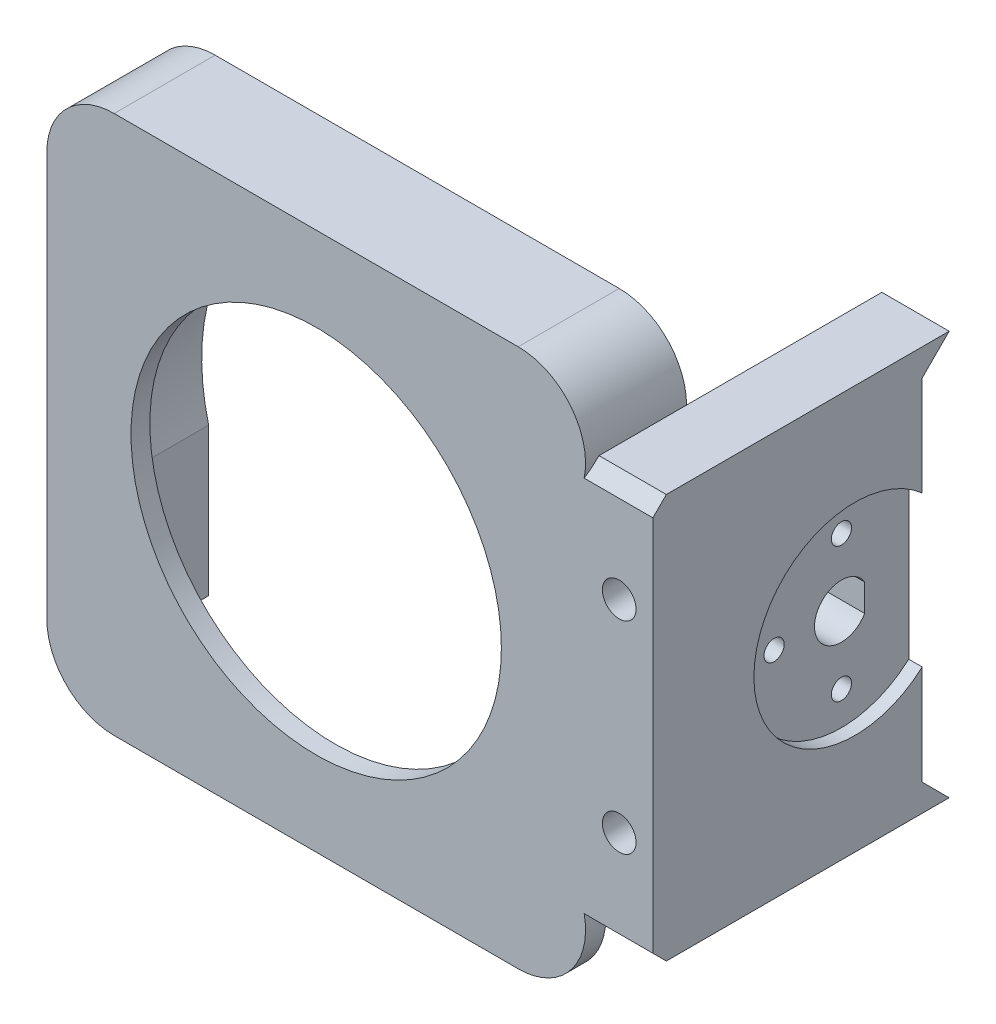
SolidWorks part; units mm, degrees
ref_plane "Front Plane" through (0, 0, 0) normal (0, 0, 1) x (1, 0, 0)
ref_plane "Top Plane" through (0, 0, 0) normal (0, 1, 0) x (1, 0, 0)
ref_plane "Right Plane" through (0, 0, 0) normal (1, 0, 0) x (0, 0, -1)
sketch "Sketch1" plane through (0, 0, 0) normal (0, 0, 1) x (1, 0, 0)
  line L1 (0, 0) -> (80, 0)
  line L2 (0, 0) -> (0, 80)
  line L3 (0, 80) -> (80, 80)
  line L4 (80, 0) -> (80, 80)
  circle A0 centre (40, 40) radius 32
  dimension "D3" = 64
  dimension "D1" = 80
  dimension "D2" = 80
extrude "Boss-Extrude1" add sketch "Sketch1" along normal blind 15
sketch "Sketch2" plane through (0, 0, 15) normal (0, 0, 1) x (1, 0, 0)
  circle A0 centre (40, 40) radius 32
  circle A1 centre (40, 40) radius 27.5
  dimension "D1" = 55
  dimension "D2" = 64
extrude "Boss-Extrude2" add sketch "Sketch2" against normal blind 2.8
fillet "Fillet1" radius 10 4 edges at (80, 0, 7.5) (0, 0, 7.5) (0, 80, 7.5) (80, 80, 7.5)
sketch "Sketch4" plane through (80, 0, 0) normal (1, 0, 0) x (0, 0, -1)
  line L1 (-15, 70) -> (25, 70)
  line L2 (-15, 70) -> (-15, 10)
  line L3 (-15, 10) -> (25, 10)
  line L4 (25, 70) -> (25, 10)
  dimension "D1" = 40
extrude "Boss-Extrude3" add sketch "Sketch4" along normal blind 10
sketch "Sketch10" plane through (0, 0, -25) normal (0, 0, -1) x (-1, 0, 0)
  line L0 (-90, 70) -> (-80, 70) construction
  line L1 (-90, 40) -> (-80, 40) construction
  line L2 (-90, 10) -> (-90, 70) construction
  line L3 (-80, 10) -> (-80, 70) construction
  circle A0 centre (-85, 55) radius 2.5
  circle A1 centre (-85, 25) radius 2.5
  dimension "D1" = 15
  dimension "D2" = 5
extrude "Cut-Extrude2" cut sketch "Sketch10" against normal through all
chamfer "Chamfer1" distance 2 angle 45 2 edges at (85, 10, 15) (85, 70, 15)
sketch "Sketch11" plane through (90, 0, 0) normal (1, 0, 0) x (0, 0, -1)
  line L0 (25, 70) -> (25, 66)
  line L1 (25, 10) -> (25, 70) construction
  line L2 (25, 66) -> (29, 70)
  line L3 (29, 70) -> (25, 70)
  line L4 (25, 40) -> (18.4514, 40) construction
  line L5 (25, 14) -> (29, 10)
  line L6 (25, 10) -> (25, 14)
  line L7 (29, 10) -> (25, 10)
  dimension "D1" = 4
  dimension "D2" = 4
extrude "Boss-Extrude7" add sketch "Sketch11" against normal blind 10
sketch "Sketch12" plane through (90, 0, 0) normal (1, 0, 0) x (0, 0, -1)
  line L0 (-15, 40) -> (15, 40) construction
  line L1 (-15, 68) -> (-15, 12) construction
  line L2 (18.4517, 42.0213) -> (18.4517, 37.9787)
  arc A0 (18.4517, 42.0213) -> (18.4517, 37.9787) centre (15, 40) ccw
  dimension "D2" = 8
  dimension "D1" = 30
extrude "Cut-Extrude3" cut sketch "Sketch12" against normal blind 10
sketch "Sketch13" plane through (90, 0, 0) normal (1, 0, 0) x (0, 0, -1)
  circle A0 centre (15, 40) radius 10
  circle A1 centre (15, 50) radius 1.5
  circle A3 centre (15, 40) radius 10
  circle A4 centre (15, 30) radius 1.5
  circle A5 centre (15, 40) radius 10
  circle A6 centre (5, 40) radius 1.5
  circle A7 centre (15, 40) radius 10
  arc A8 (24.925, 41.4981) -> (24.925, 38.5019) centre (25, 40) ccw [skipped]
  point P17 (15, 40)
  dimension "D1" = 20
  dimension "D2" = 3
  dimension "D3" = 4
extrude "Cut-Extrude5" cut sketch "Sketch13" against normal blind 30 contours A6 | A1 | A4
sketch "Sketch14" plane through (90, 0, 0) normal (1, 0, 0) x (0, 0, -1)
  circle A0 centre (15, 40) radius 15
  dimension "D1" = 30
extrude "Cut-Extrude6" cut sketch "Sketch14" against normal blind 2
sketch "Sketch16" plane through (0, 0, 0) normal (0, 0, -1) x (-1, 0, 0)
  line L1 (-70, 0) -> (-9.0323, 0)
  line L2 (-70, 0) -> (-70, 31.9378)
  line L3 (-70, 31.9378) -> (-9.0323, 31.9378)
  line L4 (-9.0323, 0) -> (-9.0323, 31.9378)
  circle A0 centre (-40, 40) radius 32 construction
extrude "Cut-Extrude10" cut sketch "Sketch16" against normal blind 12
sketch "Sketch17" plane through (0, 0, 0) normal (0, 0, -1) x (-1, 0, 0)
  line L1 (-80, 10) -> (0, 10)
  line L2 (-80, 10) -> (-80, 0)
  line L3 (-80, 0) -> (0, 0)
  line L4 (0, 10) -> (0, 0)
extrude "Cut-Extrude11" cut sketch "Sketch17" against normal blind 12
sketch "Sketch18" plane through (0, 10, 0) normal (0, -1, 0) x (1, 0, 0)
  circle A0 centre (5, 6) radius 2
  circle A1 centre (75, 6) radius 2
  dimension "D1" = 4
  dimension "D2" = 4
extrude "Cut-Extrude12" cut sketch "Sketch18" against normal blind 20
sketch "Sketch19" plane through (0, 30, 0) normal (0, -1, 0) x (1, 0, 0)
